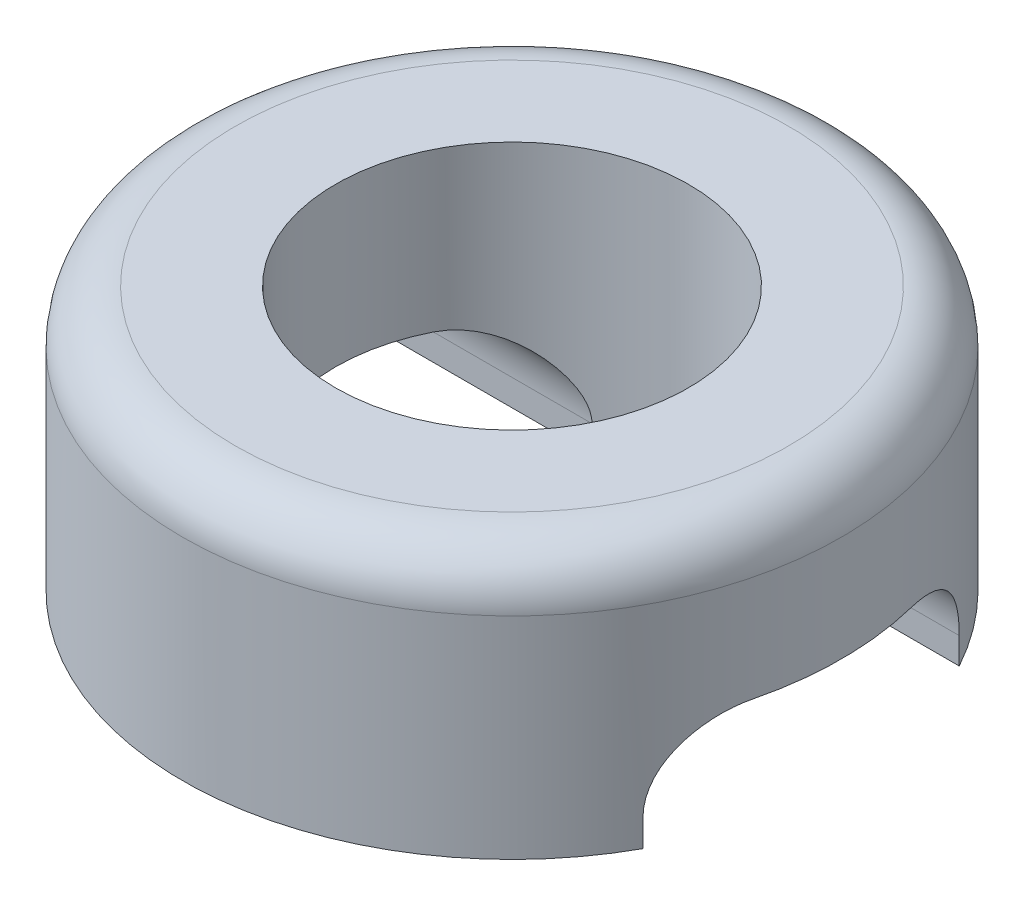
SolidWorks part; units mm, degrees
ref_plane "Front Plane" through (0, 0, 0) normal (0, 0, 1) x (1, 0, 0)
ref_plane "Top Plane" through (0, 0, 0) normal (0, 1, 0) x (1, 0, 0)
ref_plane "Right Plane" through (0, 0, 0) normal (1, 0, 0) x (0, 0, -1)
sketch "Sketch1" plane through (0, 0, 0) normal (0, 1, 0) x (1, 0, 0)
  circle A0 centre (0, 0) radius 4.25
  circle A1 centre (0, 0) radius 7.9375
  dimension "D1" = 8.5
  dimension "D2" = 15.875
extrude "Boss-Extrude1" add sketch "Sketch1" along normal blind 6.35
sketch "Sketch2" plane through (0, 0, 0) normal (1, 0, 0) x (0, 0, -1)
  line L5 (-7.9375, 0) -> (7.9375, 0) construction
  line L6 (3.81, 0) -> (-3.81, 0)
  line L7 (0, 0) -> (0, 2.54) construction
  line L8 (3.81, 2.54) -> (-3.81, 2.54)
  line L9 (3.81, 2.54) -> (3.81, 0)
  line L10 (-3.81, 2.54) -> (-3.81, 0)
  point P16 (0, 0)
  point P22 (0, 2.54)
  dimension "D5" = 7.62
  dimension "D6" = 2.54
extrude "Cut-Extrude1" cut sketch "Sketch2" against normal through all and the other way through all
fillet "Fillet2" radius 1.905 4 edges at (4.4233, 2.54, -3.81) (-4.4233, 2.54, -3.81) (4.4233, 2.54, 3.81) (-4.4233, 2.54, 3.81)
fillet "Fillet3" radius 1.27 1 edges at (0, 6.35, 7.9375)
